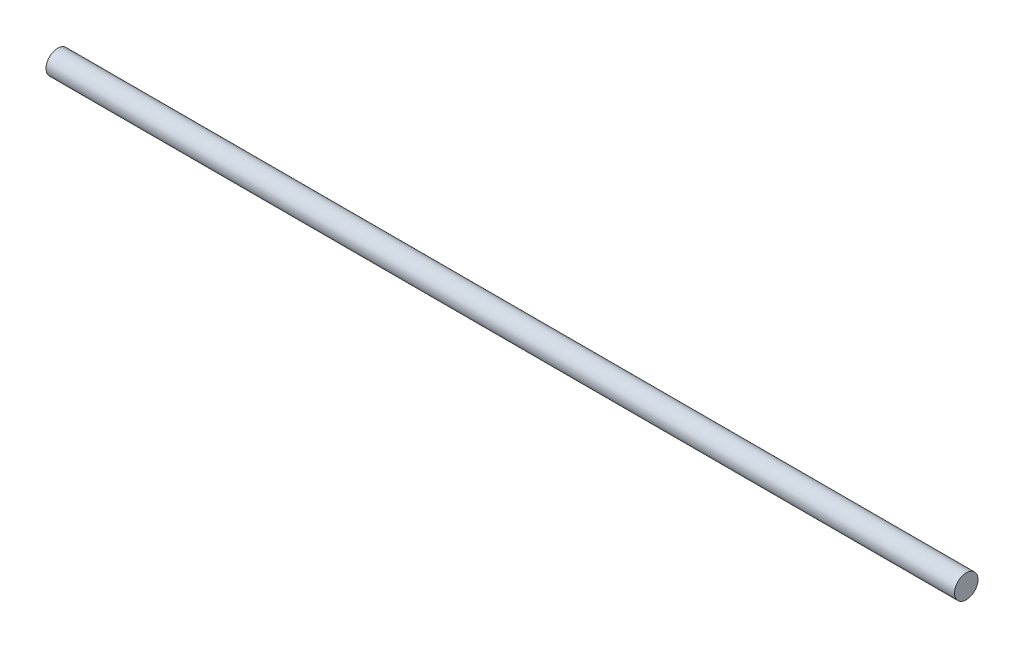
SolidWorks part; units mm, degrees
ref_plane "Alzado" through (0, 0, 0) normal (0, 0, 1) x (1, 0, 0)
ref_plane "Planta" through (0, 0, 0) normal (0, 1, 0) x (1, 0, 0)
ref_plane "Vista lateral" through (0, 0, 0) normal (1, 0, 0) x (0, 0, -1)
sketch "Croquis1" plane through (0, 0, 0) normal (1, 0, 0) x (0, 0, -1)
  circle A0 centre (0, 0) radius 4
extrude "Saliente-Extruir1" add sketch "Croquis1" along normal mid plane 310
